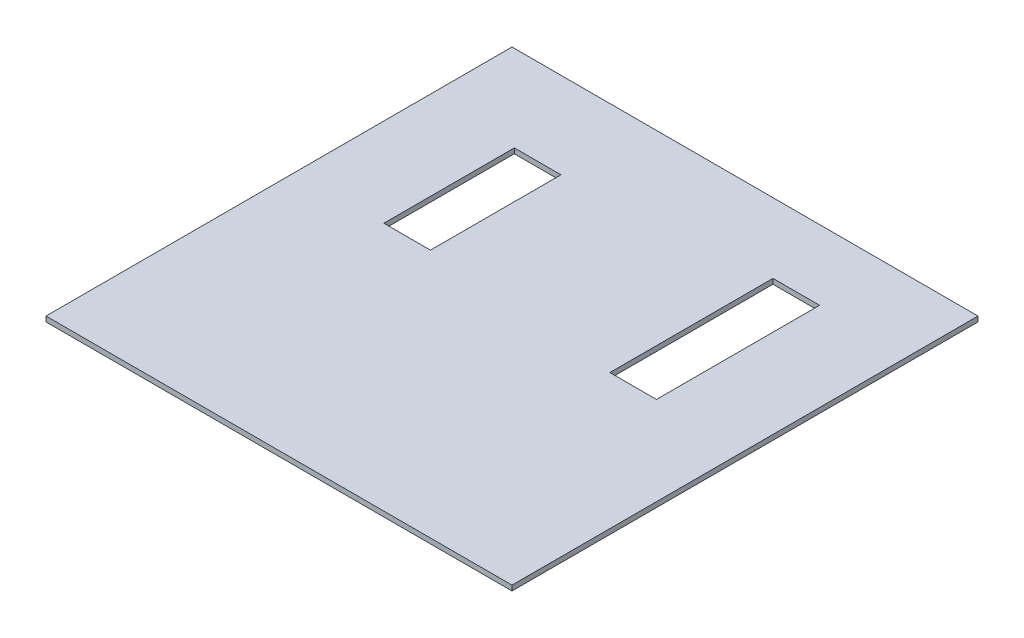
SolidWorks part; units mm, degrees
material "A-Glass Fiber"
ref_plane "Front Plane" through (0, 0, 0) normal (0, 0, 1) x (1, 0, 0)
ref_plane "Top Plane" through (0, 0, 0) normal (0, 1, 0) x (1, 0, 0)
ref_plane "Right Plane" through (0, 0, 0) normal (1, 0, 0) x (0, 0, -1)
sketch "Sketch1" plane through (0, 0, 0) normal (0, 1, 0) x (1, 0, 0)
  line L1 (0, 0) -> (25.4, 0)
  line L2 (0, 0) -> (0, 25.4)
  line L3 (0, 25.4) -> (25.4, 25.4)
  line L4 (25.4, 0) -> (25.4, 25.4)
  dimension "D1" = 25.4
  dimension "D2" = 25.4
extrude "Boss-Extrude1" add sketch "Sketch1" along normal blind 0.2794
sketch "Sketch2" plane through (0, 0.2794, 0) normal (0, 1, 0) x (1, 0, 0)
  line L1 (4.826, 20.701) -> (4.826, 13.589)
  line L3 (4.826, 13.589) -> (7.366, 13.589)
  line L4 (7.366, 20.701) -> (7.366, 13.589)
  line L5 (0, 0) -> (25.4, 0) construction
  line L7 (18.034, 21.59) -> (18.034, 12.7)
  line L8 (18.034, 12.7) -> (20.574, 12.7)
  line L9 (20.574, 21.59) -> (20.574, 12.7)
  line L10 (0, 0) -> (25.4, 0) construction
  line L11 (4.826, 20.701) -> (7.366, 20.701)
  line L12 (18.034, 21.59) -> (20.574, 21.59)
  point P10 (12.7, 0)
  point P13 (12.7, 0)
  dimension "D1" = 8.89
  dimension "D2" = 12.7
  dimension "D3" = 2.54
  dimension "D4" = 2.54
  dimension "D5" = 5.334
  dimension "D6" = 5.334
  dimension "D7" = 7.112
  dimension "D8" = 13.589
extrude "Cut-Extrude1" cut sketch "Sketch2" against normal through all
